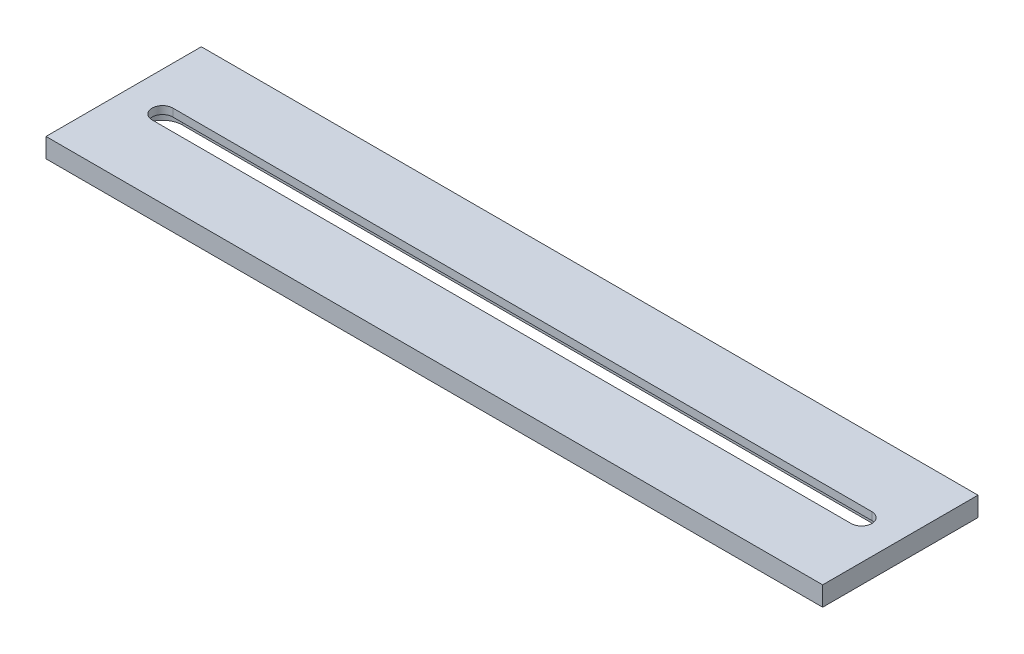
SolidWorks part; units mm, degrees
ref_plane "Front Plane" through (0, 0, 0) normal (0, 0, 1) x (1, 0, 0)
ref_plane "Top Plane" through (0, 0, 0) normal (0, 1, 0) x (1, 0, 0)
ref_plane "Right Plane" through (0, 0, 0) normal (1, 0, 0) x (0, 0, -1)
sketch "Sketch1" plane through (0, 0, 0) normal (0, 1, 0) x (1, 0, 0)
  line L1 (-127, -25.4) -> (127, -25.4)
  line L2 (-127, -25.4) -> (-127, 25.4)
  line L3 (-127, 25.4) -> (127, 25.4)
  line L4 (127, -25.4) -> (127, 25.4)
  line L5 (-127, -25.4) -> (127, 25.4) construction
  line L6 (-127, 25.4) -> (127, -25.4) construction
  point P0 (0, 0)
  dimension "D1" = 254
  dimension "D2" = 50.8
extrude "Boss-Extrude1" add sketch "Sketch1" along normal blind 6.35
sketch "Sketch2" plane through (0, 6.35, 0) normal (0, 1, 0) x (1, 0, 0)
  line L0 (-127, 0) -> (127, 0) construction
  line L1 (-127, 25.4) -> (-127, -25.4) construction
  line L2 (127, -25.4) -> (127, 25.4) construction
  line L3 (-114.3, 0) -> (114.3, 0) construction
  line L4 (-114.3, 3.3782) -> (114.3, 3.3782)
  line L5 (-114.3, -3.3782) -> (114.3, -3.3782)
  arc A0 (-114.3, 3.3782) -> (-114.3, -3.3782) centre (-114.3, 0) ccw
  arc A1 (114.3, -3.3782) -> (114.3, 3.3782) centre (114.3, 0) ccw
  point P8 (0, 0)
  dimension "D1" = 6.7564
  dimension "D2" = 228.6
extrude "Cut-Extrude1" cut sketch "Sketch2" against normal through all
sketch "Sketch3" plane through (0, 0, 0) normal (0, -1, 0) x (1, 0, 0)
  line L0 (-114.3, 0) -> (114.3, 0) construction
  line L1 (-114.3, 6.477) -> (114.3, 6.477)
  line L2 (-114.3, -6.477) -> (114.3, -6.477)
  arc A0 (-114.3, 6.477) -> (-114.3, -6.477) centre (-114.3, 0) ccw
  arc A1 (114.3, -6.477) -> (114.3, 6.477) centre (114.3, 0) ccw
  point P2 (0, 0)
  dimension "D1" = 12.954
extrude "Cut-Extrude2" cut sketch "Sketch3" against normal blind 3.81
